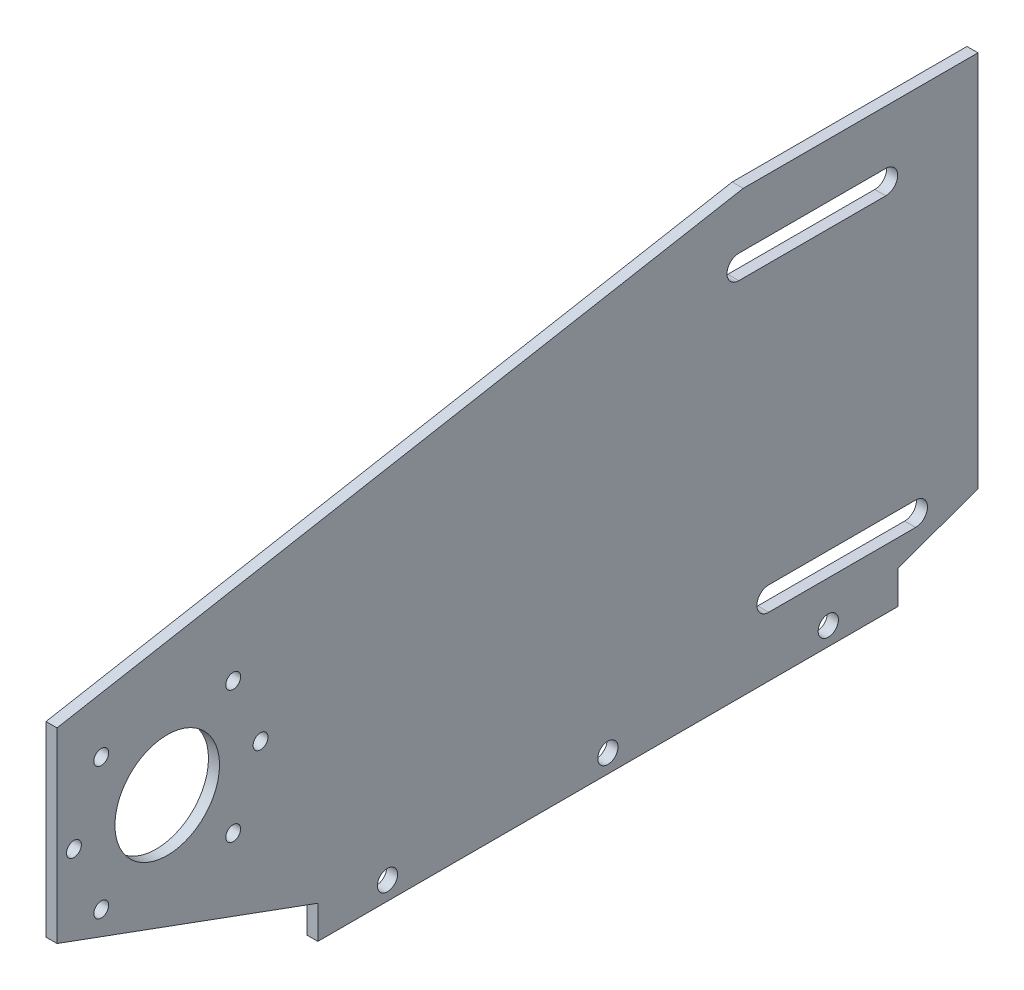
SolidWorks part; units mm, degrees
ref_plane "Front Plane" through (0, 0, 0) normal (0, 0, 1) x (1, 0, 0)
ref_plane "Top Plane" through (0, 0, 0) normal (0, 1, 0) x (1, 0, 0)
ref_plane "Right Plane" through (0, 0, 0) normal (1, 0, 0) x (0, 0, -1)
sketch "Sketch1" plane through (0, 0, 0) normal (1, 0, 0) x (0, 0, -1)
  line L1 (0, 0) -> (300, 0)
  line L2 (0, 0) -> (0, 150)
  line L3 (0, 150) -> (300, 150)
  line L4 (300, 0) -> (300, 150)
  circle A0 centre (30, 55) radius 14.235
  dimension "D1" = 300
  dimension "D5" = 28.47
  dimension "D4" = 55
  dimension "D2" = 150
  dimension "D3" = 30
extrude "Boss-Extrude1" add sketch "Sketch1" along normal blind 3
sketch "Sketch2" plane through (0, 0, 0) normal (-1, 0, 0) x (0, 0, 1)
  line L0 (-225.6114, 104.9384) -> (-185.6114, 104.9384) construction
  line L3 (-185.6114, 98.4784) -> (-225.6114, 98.4784) construction
  line L6 (-193.7436, 16.2317) -> (-233.7436, 16.2317) construction
  line L11 (-233.7436, 22.6817) -> (-193.7436, 22.6817) construction
  line L14 (0, 0) -> (-300, 0) construction
  line L17 (0, 150) -> (0, 0) construction
  line L18 (-225.6114, 104.9384) -> (-185.6114, 104.9384)
  line L19 (-185.6114, 98.4784) -> (-225.6114, 98.4784)
  line L20 (-193.7436, 16.2317) -> (-233.7436, 16.2317)
  line L21 (-233.7436, 22.6817) -> (-193.7436, 22.6817)
  arc A2 (-225.6114, 104.9384) -> (-225.6114, 98.4784) centre (-225.6114, 101.7084) ccw construction
  circle A12 centre (-10, 110) radius 3.225
  arc A14 (-185.6114, 98.4784) -> (-185.6114, 104.9384) centre (-185.6114, 101.7084) ccw construction
  arc A15 (-193.7436, 16.2317) -> (-193.7436, 22.6817) centre (-193.7436, 19.4567) ccw construction
  arc A16 (-233.7436, 22.6817) -> (-233.7436, 16.2317) centre (-233.7436, 19.4567) ccw construction
  arc A17 (-225.6114, 104.9384) -> (-225.6114, 98.4784) centre (-225.6114, 101.7084) ccw
  arc A18 (-185.6114, 98.4784) -> (-185.6114, 104.9384) centre (-185.6114, 101.7084) ccw
  arc A19 (-193.7436, 16.2317) -> (-193.7436, 22.6817) centre (-193.7436, 19.4567) ccw
  arc A20 (-233.7436, 22.6817) -> (-233.7436, 16.2317) centre (-233.7436, 19.4567) ccw
  dimension "D14" = 6.45
  dimension "D20" = 10
  dimension "D21" = 110
extrude "Cut-Extrude1" cut sketch "Sketch2" against normal up to next
sketch "Sketch4" plane through (3, 0, 0) normal (1, 0, 0) x (0, 0, -1)
  line L4 (0, 150) -> (0, 0)
  line L5 (0, 0) -> (300, 0)
  line L6 (300, 0) -> (300, 150)
  line L7 (300, 150) -> (0, 150)
  line L8 (0, 150) -> (0, 0)
  line L9 (0, 0) -> (300, 0)
  line L10 (300, 0) -> (300, 150)
  line L11 (300, 150) -> (0, 150)
  circle A0 centre (47.9605, 37.0395) radius 2.0193 construction
  circle A1 centre (47.9605, 37.0395) radius 2.0193
  circle A2 centre (47.9605, 72.9605) radius 2.0193 construction
  circle A3 centre (47.9605, 72.9605) radius 2.0193
  circle A4 centre (55.4, 55) radius 2.0193 construction
  circle A5 centre (55.4, 55) radius 2.0193
  circle A6 centre (12.0395, 72.9605) radius 2.0193 construction
  circle A7 centre (12.0395, 72.9605) radius 2.0193
  circle A8 centre (4.6, 55) radius 2.0193 construction
  circle A9 centre (4.6, 55) radius 2.0193
  circle A10 centre (12.0395, 37.0395) radius 2.0193 construction
  circle A11 centre (12.0395, 37.0395) radius 2.0193
  dimension "D1" = 0
extrude "Cut-Extrude4" cut sketch "Sketch4" against normal through all contours A11 | A7 | A9 | A1 | A5 | A3 region at (3, 37.0395, -12.0395)
sketch "Sketch5" plane through (0, 0, 0) normal (-1, 0, 0) x (0, 0, 1)
  line L7 (-71, 0) -> (-71, 9) construction
  line L8 (-71, 9) -> (0, 35) construction
  line L9 (-71, 0) -> (-71, 9)
  line L10 (-71, 9) -> (0, 35)
  line L11 (0, 35) -> (0, 0)
  line L12 (0, 0) -> (-71, 0)
  line L13 (0, 85.8486) -> (-186.8026, 119.6415) construction
  line L14 (0, 85.8486) -> (-186.8026, 119.6415)
  line L16 (-300, 150) -> (0, 150) construction
  line L17 (0, 150) -> (0, 85.8486)
  line L19 (-300.3105, 150) -> (0, 150)
  line L20 (-186.8026, 119.6415) -> (-250.718, 119.6415) construction
  line L21 (-186.8026, 119.6415) -> (-300.3105, 119.6415)
  line L22 (-300.3105, 119.6415) -> (-300.3105, 150)
  point P8 (-300, 150)
extrude "Cut-Extrude5" cut sketch "Sketch5" against normal through all
sketch "Sketch6" plane through (0, 0, 0) normal (-1, 0, 0) x (0, 0, 1)
  line L8 (-250.718, 119.6415) -> (-250.718, 16.8759) construction
  line L9 (-228.924, 9) -> (-228.924, 0) construction
  line L10 (-250.718, 16.8759) -> (-228.924, 9) construction
  line L11 (-250.718, 165.7129) -> (-250.718, 16.8759)
  line L12 (-228.924, 9) -> (-228.924, 0)
  line L13 (-250.718, 16.8759) -> (-228.924, 9)
  line L14 (-250.718, 165.7129) -> (-364.8309, 165.7129)
  line L15 (-364.8309, 165.7129) -> (-355.7689, 0)
  line L16 (-355.7689, 0) -> (-228.924, 0)
  line M6 (-300, 119.6415) -> (-300, 0)
  line M7 (-300, 0) -> (-71, 0)
extrude "Cut-Extrude6" cut sketch "Sketch6" against normal blind 10 contours L11 M7 M6 region at (0, 82.816, -304.5522)
sketch "Sketch7" plane through (3, 0, 0) normal (1, 0, 0) x (0, 0, -1)
  line L1 (71, 0) -> (228.924, 0) construction
  circle A0 centre (89.962, 5) radius 2.75
  circle A1 centre (149.962, 5) radius 2.75
  circle A2 centre (209.962, 5) radius 2.75
  point P8 (211.2386, -13.5473)
  point P9 (149.962, 0)
  point P10 (0, 0)
  dimension "D1" = 5.5
  dimension "D2" = 5.5
  dimension "D3" = 5.5
  dimension "D4" = 60
  dimension "D5" = 60
  dimension "D6" = 5
extrude "Cut-Extrude7" cut sketch "Sketch7" against normal through all
